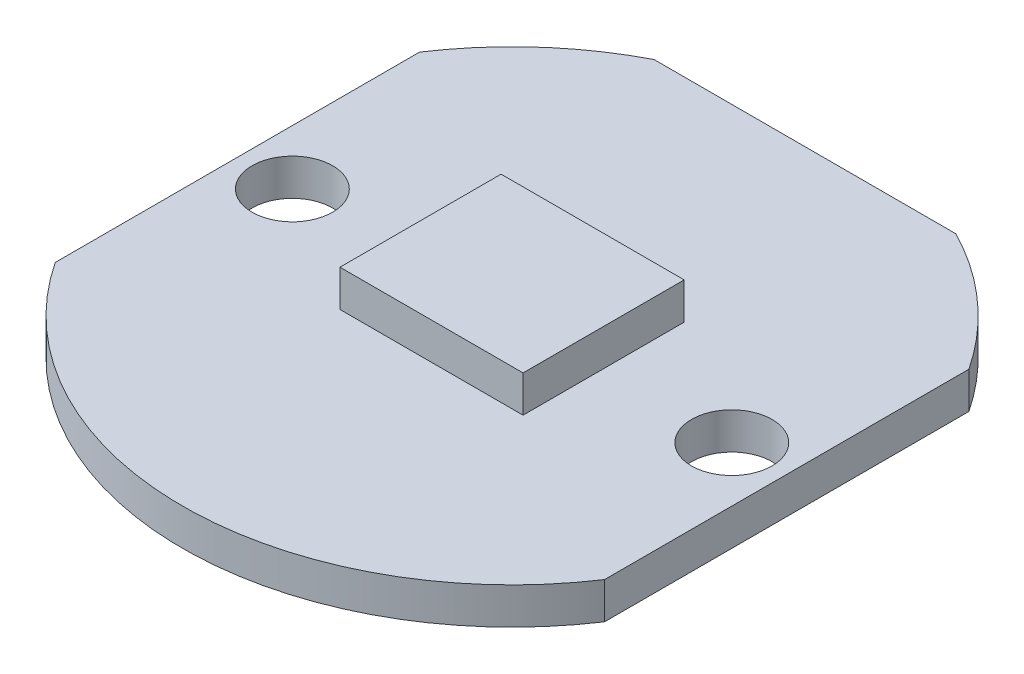
SolidWorks part; units mm, degrees
ref_plane "Front" through (0, 0, 0) normal (0, 0, 1) x (1, 0, 0)
ref_plane "Top" through (0, 0, 0) normal (0, 1, 0) x (1, 0, 0)
ref_plane "Right" through (0, 0, 0) normal (1, 0, 0) x (0, 0, -1)
sketch "Эскиз1" plane through (0, 0, 0) normal (0, 1, 0) x (1, 0, 0)
  line L0 (0, 0) -> (0, 24.3532) construction
  line L1 (0, 0) -> (-41.2832, 0) construction
  line L2 (-7.5, 8) -> (7.5, 8)
  line L3 (-7.5, 8) -> (-7.5, -4.9749)
  line L4 (7.5, 8) -> (7.5, -4.9749)
  circle A0 centre (0, 0) radius 9
  circle A1 centre (0, 0) radius 6 construction
  circle A2 centre (-6, 0) radius 1.1
  circle A4 centre (6, 0) radius 1.1
  point P9 (0, -9)
  dimension "D1" = 18
  dimension "D5" = 2.2
  dimension "D2" = 17
  dimension "D3" = 15
  dimension "D4" = 7.5
extrude "Бобышка-Вытянуть1" add sketch "Эскиз1" along normal blind 1 contours L4 A0 L2 L3 A4 A2 region at (0, 0, 0.2114)
sketch "Эскиз3" plane through (0, 0, 0) normal (0, 1, 0) x (1, 0, 0)
  line L1 (2.5, -2.2) -> (-2.5, -2.2)
  line L2 (2.5, -2.2) -> (2.5, 2.2)
  line L3 (2.5, 2.2) -> (-2.5, 2.2)
  line L4 (-2.5, -2.2) -> (-2.5, 2.2)
  line L5 (2.5, -2.2) -> (-2.5, 2.2) construction
  line L6 (2.5, 2.2) -> (-2.5, -2.2) construction
  point P0 (0, 0)
  dimension "D1" = 5
  dimension "D2" = 4.4
extrude "Бобышка-Вытянуть2" add sketch "Эскиз3" along normal blind 1 from offset 1 separate body
